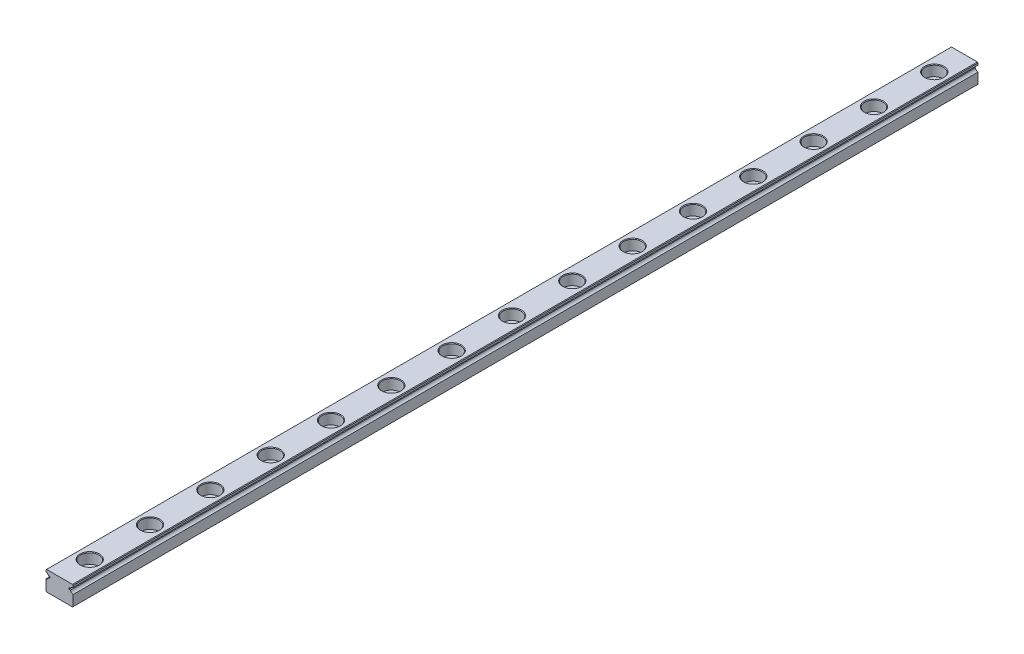
SolidWorks part; units mm, degrees
ref_plane "Спереди" through (0, 0, 0) normal (0, 0, 1) x (1, 0, 0)
ref_plane "Сверху" through (0, 0, 0) normal (0, 1, 0) x (1, 0, 0)
ref_plane "Справа" through (0, 0, 0) normal (1, 0, 0) x (0, 0, -1)
sketch "Sketch1" plane through (0, 0, 0) normal (0, 0, 1) x (1, 0, 0)
  line L0 (0, 0) -> (0, 4.3706) construction
  line L1 (-4.3, -3.25) -> (4.3, -3.25)
  line L2 (-4.5, -3.05) -> (-4.5, 0.455)
  line L3 (-4.3, 3.25) -> (4.3, 3.25)
  line L4 (4.5, -3.05) -> (4.5, 0.455)
  line L5 (-4.5, -3.25) -> (4.5, 3.25) construction
  line L6 (-4.5, 3.25) -> (4.5, -3.25) construction
  line L7 (-4.5, 2.445) -> (-4.5, 3.05)
  line L8 (4.5, 2.445) -> (4.5, 3.05)
  line L9 (-4.5, -3.05) -> (-4.3, -3.25)
  line L10 (4.3, -3.25) -> (4.5, -3.05)
  line L11 (4.3, 3.25) -> (4.5, 3.05)
  line L12 (-4.5, 3.05) -> (-4.3, 3.25)
  line L13 (3.6177, 1.2625) -> (3.1501, 1.2625)
  line L14 (-3.6177, 1.2625) -> (-3.1501, 1.2625)
  line L15 (3.1501, 1.2625) -> (3.1501, 1.7625)
  line L16 (-3.6501, 1.7625) -> (-3.1501, 1.7625)
  line L17 (-3.1501, 1.2625) -> (-3.1501, 1.7625)
  line L18 (3.6501, 1.7625) -> (3.1501, 1.7625)
  arc A0 (-4.5, 2.445) -> (-3.6501, 1.7625) centre (-4.6, 1.45) cw
  arc A1 (4.5, 2.445) -> (3.6501, 1.7625) centre (4.6, 1.45) ccw
  arc A2 (-3.6177, 1.2625) -> (-4.5, 0.455) centre (-4.6, 1.45) cw
  arc A3 (3.6177, 1.2625) -> (4.5, 0.455) centre (4.6, 1.45) ccw
  point P0 (0, 0)
  dimension "D4" = 1
  dimension "D5" = 0.1
  dimension "D1" = 9
  dimension "D2" = 6.5
  dimension "D3" = 1.8
  dimension "D6" = 0.5
  dimension "D7" = 0.5
extrude "Extrude1" add sketch "Sketch1" along normal blind 300
sketch "Sketch2" plane through (0, 3.25, 0) normal (0, 1, 0) x (1, 0, 0)
  line L0 (0, 0) -> (0, -10) construction
  circle A0 centre (0, -10) radius 1.75
  circle A1 centre (0, -10) radius 3
  dimension "D1" = 3.5
  dimension "D2" = 6
  dimension "D3" = 10
extrude "Extrude2" cut sketch "Sketch2" against normal up to next contours A0 region at (0, 3.25, 10)
extrude "Extrude4" cut sketch "Sketch" against normal blind 3.5
sketch "Sketch" plane through (0, 3.25, 0) normal (0, 1, 0) x (1, 0, 0) same geometry as "Sketch2"
chamfer "Chamfer1" distance 0.2 angle 45 2 edges at (0, -3.25, 11.75) (0, 3.25, 13)
pattern_linear "LPattern1" count 15 spacing 20 along (0, 0, 1) of "Extrude4", "Chamfer1", "Extrude2"
